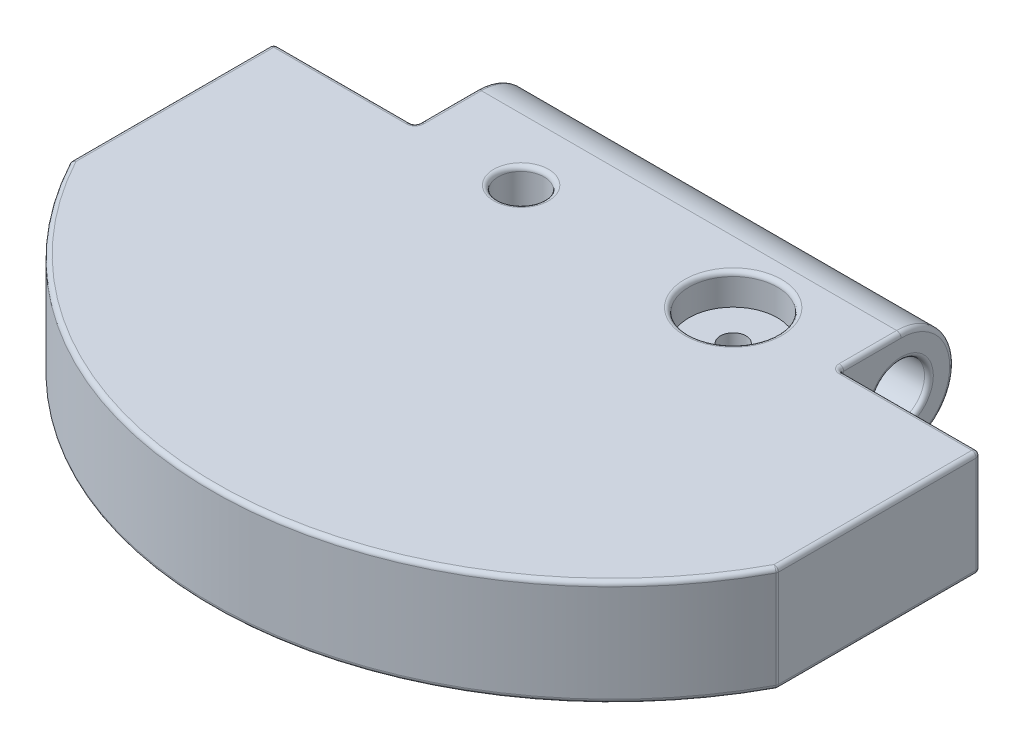
SolidWorks part; units mm, degrees
ref_plane "Front Plane" through (0, 0, 0) normal (0, 0, 1) x (1, 0, 0)
ref_plane "Top Plane" through (0, 0, 0) normal (0, 1, 0) x (1, 0, 0)
ref_plane "Right Plane" through (0, 0, 0) normal (1, 0, 0) x (0, 0, -1)
sketch "Sketch1" plane through (0, 0, 0) normal (0, 1, 0) x (1, 0, 0)
  line L1 (-40, -30) -> (40, -30)
  line L2 (-40, -30) -> (-40, 30)
  line L3 (-40, 30) -> (40, 30)
  line L4 (40, -30) -> (40, 30)
  line L5 (-40, -30) -> (40, 30) construction
  line L6 (-40, 30) -> (40, -30) construction
  line L7 (-24, 30) -> (-40, 30)
  line L8 (-24, 30) -> (-24, 17)
  line L9 (-24, 17) -> (-40, 17)
  line L10 (-40, 30) -> (-40, 17)
  line L11 (24, 30) -> (40, 30)
  line L12 (24, 30) -> (24, 17)
  line L13 (24, 17) -> (40, 17)
  line L14 (40, 30) -> (40, 17)
  arc A0 (-40, -6) -> (40, -6) centre (0, 15.3333) ccw
  point P0 (0, 0)
  dimension "D1" = 80
  dimension "D2" = 60
  dimension "D3" = 48
  dimension "D4" = 13
  dimension "D5" = 13
  dimension "D6" = 24
  dimension "D7" = 24
extrude "Boss-Extrude1" add sketch "Sketch1" along normal blind 12 contours A0 L4 L13 L12 L3 L8 L9 L2 region at (0, 0, -0.8069)
fillet "Fillet1" radius 6 2 edges at (0, 0, -30) (0, 12, -30)
sketch "Sketch2" plane through (-24, 0, 0) normal (-1, 0, 0) x (0, 0, 1)
  circle A0 centre (-24, 6) radius 3.15
  dimension "D1" = 6.3
extrude "Cut-Extrude1" cut sketch "Sketch2" against normal blind 70 contours A0
sketch "Sketch3" plane through (0, 12, 0) normal (0, 1, 0) x (1, 0, 0)
  line L0 (-24, 17) -> (0, 17) construction
  line L3 (0, 17) -> (24, 17) construction
  circle A0 centre (-12, 17) radius 1.45
  circle A1 centre (12, 17) radius 1.45
  circle A2 centre (-12, 17) radius 2.6
  circle A3 centre (12, 17) radius 2.6
  circle A4 centre (12, 17) radius 5
  circle A5 centre (-12, 17) radius 5
  dimension "D1" = 2.9
  dimension "D2" = 2.9
  dimension "D3" = 5.2
  dimension "D4" = 5.2
  dimension "D5" = 10
  dimension "D6" = 10
extrude "Cut-Extrude2" cut sketch "Sketch3" along normal blind 3.5 from surface contours A5 starting at face at (0, 0, -10)
extrude "Cut-Extrude3" cut sketch "Sketch3<3>" against normal blind 13.5 contours A0
sketch "Sketch3<3>" plane through (0, 12, 0) normal (0, 1, 0) x (1, 0, 0) same geometry as "Sketch3"
extrude "Cut-Extrude4" cut sketch "Sketch3<4>" against normal blind 4.4 contours A2
sketch "Sketch3<4>" plane through (0, 12, 0) normal (0, 1, 0) x (1, 0, 0) same geometry as "Sketch3"
extrude "Cut-Extrude5" cut sketch "Sketch3<5>" against normal blind 3.5 contours A4
sketch "Sketch3<5>" plane through (0, 12, 0) normal (0, 1, 0) x (1, 0, 0) same geometry as "Sketch3"
extrude "Cut-Extrude6" cut sketch "Sketch3<6>" against normal blind 18 contours A1
sketch "Sketch3<6>" plane through (0, 12, 0) normal (0, 1, 0) x (1, 0, 0) same geometry as "Sketch3"
extrude "Cut-Extrude7" cut sketch "Sketch3<7>" along normal blind 4.4 from surface contours A3 starting at face at (12, 0, -15.55)
sketch "Sketch3<7>" plane through (0, 12, 0) normal (0, 1, 0) x (1, 0, 0) same geometry as "Sketch3"
fillet "Fillet2" radius 0.5 30 edges at (24, 10.2426, -28.2426) (24, 1.7574, -28.2426) (24, 6, -27.15) (40, 6, -17) (24, 6, -17) (-24, 6, -17) (-24, 1.7574, -28.2426) (-24, 10.2426, -28.2426) (-24, 6, -20.85) (-32, 0, -17) (40, 0, -5.5) (32, 0, -17) (24, 0, -20.5) (-24, 0, -20.5) (-12, 0, -12) (12, 0, -14.4) (40, 6, 6) (0, 0, 30) (-40, 6, -17) (-40, 6, 6) (-40, 0, -5.5) (32, 12, -17) (40, 12, -5.5) (0, 12, 30) (-40, 12, -5.5) (-32, 12, -17) (-24, 12, -20.5) (24, 12, -20.5) (-12, 12, -14.4) (12, 12, -12)
